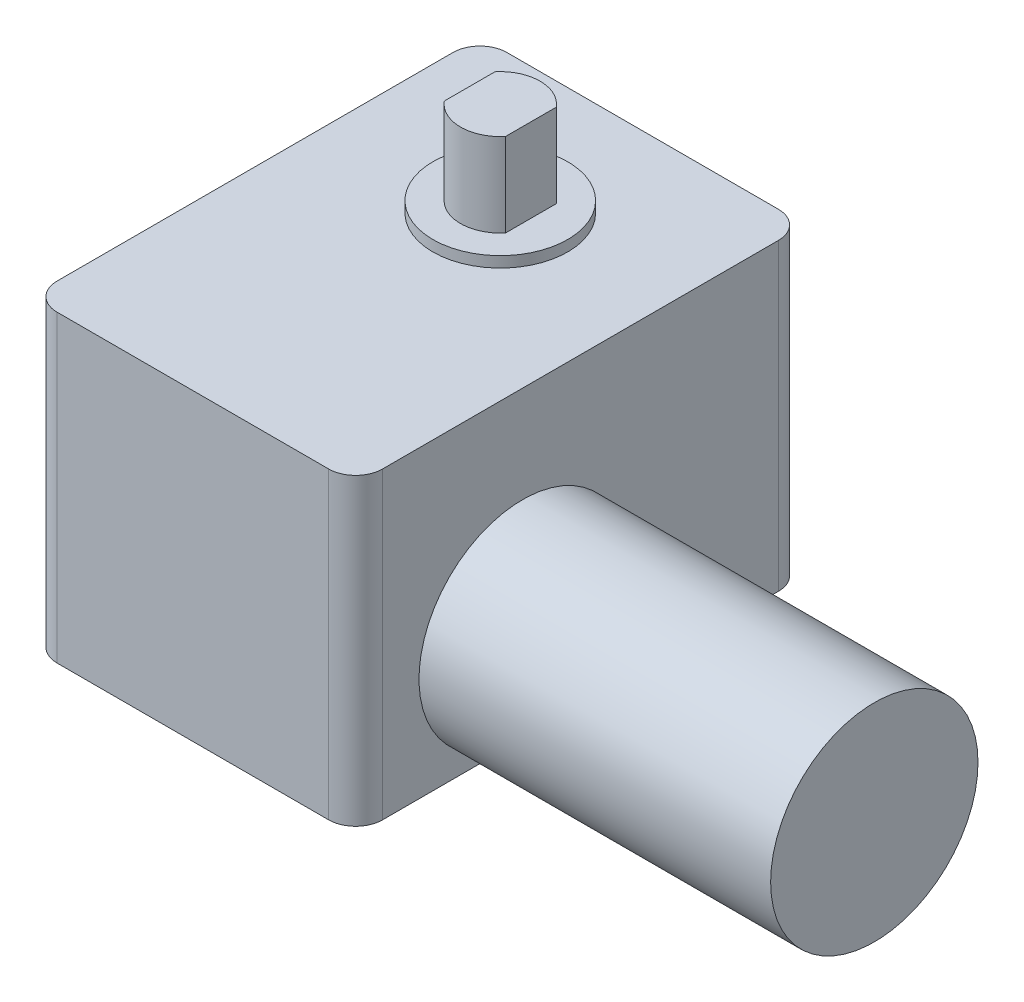
SolidWorks part; units mm, degrees
material "Delrin 2700 NC010, Low Viscosity Acetal Copolymer (SS)"
ref_plane "Front Plane" through (0, 0, 0) normal (0, 0, 1) x (1, 0, 0)
ref_plane "Top Plane" through (0, 0, 0) normal (0, 1, 0) x (1, 0, 0)
ref_plane "Right Plane" through (0, 0, 0) normal (1, 0, 0) x (0, 0, -1)
sketch "Sketch2" plane through (0, 0, 0) normal (0, 1, 0) x (1, 0, 0)
  line L0 (0, 0) -> (0, 16.68)
  line L1 (0, 0) -> (12.07, 0)
  line L2 (0, 16.68) -> (12.07, 16.68)
  line L3 (12.07, 0) -> (12.07, 16.68)
  line L4 (12.07, 2.35) -> (12.07, 10.04)
  line L5 (12.07, 2.35) -> (25.11, 2.35)
  line L7 (25.11, 2.35) -> (25.11, 6.195)
  line L8 (4.8983, 12.34) -> (4.8983, 10.46)
  line L9 (7.1717, 12.34) -> (7.1717, 10.46)
  line L10 (25.11, 6.195) -> (12.07, 6.195)
  circle A0 centre (6.035, 11.4) radius 2.5
  arc A1 (4.8983, 10.46) -> (7.1717, 10.46) centre (6.035, 11.4) ccw
  arc A2 (7.1717, 12.34) -> (4.8983, 12.34) centre (6.035, 11.4) ccw
  point P11 (6.035, 16.68)
  dimension "D7" = 5
  dimension "D8" = 2.95
  dimension "D1" = 12.07
  dimension "D2" = 16.68
  dimension "D3" = 2.35
  dimension "D4" = 3.845
  dimension "D5" = 25.11
  dimension "D6" = 11.4
  dimension "D9" = 1.88
revolve "Revolve1" add sketch "Sketch2" angle 360 about L10 region at (18.59, 0, -4.2725)
extrude "Boss-Extrude1" add sketch "Sketch2<5>" against normal blind 3.845 contours L1 L3 L4 L2 L0 A0 | A0 A2 L9 A1 L8 | L9 A2 L8 A1 region at (6.035, 0, -8.0093) region at (6.035, 0, -11.4) region at (3.6057, 0, -11.4)
sketch "Sketch2<5>" plane through (0, 0, 0) normal (0, 1, 0) x (1, 0, 0) same geometry as "Sketch2"
extrude "Boss-Extrude2" add sketch "Sketch2<6>" along normal blind 7.425 contours L1 L3 L4 L2 L0 A0 region at (6.035, 0, -8.0093)
sketch "Sketch2<6>" plane through (0, 0, 0) normal (0, 1, 0) x (1, 0, 0) same geometry as "Sketch2"
extrude "Boss-Extrude3" add sketch "Sketch2<7>" along normal blind 7.825 contours A0 A2 L9 A1 L8 region at (3.6057, 0, -11.4)
sketch "Sketch2<7>" plane through (0, 0, 0) normal (0, 1, 0) x (1, 0, 0) same geometry as "Sketch2"
extrude "Boss-Extrude4" add sketch "Sketch2<8>" along normal blind 10.925 contours L9 A2 L8 A1 region at (6.035, 0, -11.4)
sketch "Sketch2<8>" plane through (0, 0, 0) normal (0, 1, 0) x (1, 0, 0) same geometry as "Sketch2"
fillet "Fillet1" radius 1 4 edges at (0, 1.79, 0) (12.07, 1.79, 0) (12.07, 1.79, -16.68) (0, 1.79, -16.68)
equation "\"whitemotordepth\"=11.27mm"
equation "\"D1@Boss-Extrude2\"=\"whitemotordepth\" - \"whitemotorbackdepth\""
equation "\"whitemotorbackdepth\"=3.845mm"
equation "\"D1@Boss-Extrude1\"=\"whitemotorbackdepth\""
equation "\"D1@Boss-Extrude3\"=\"whitemotordepth\"-\"whitemotorbackdepth\"+.4"
equation "\"whitemotoraxledepth\" = 3.5mm"
equation "\"D1@Boss-Extrude4\"=\"whitemotoraxledepth\"+\"whitemotordepth\"-\"whitemotorbackdepth\""
equation "\"whitemotoraxleoffset\"=11.4mm"
equation "\"D6@Sketch2\"=\"whitemotoraxleoffset\""
equation "\"whitemotorwidth\"=12.07mm"
equation "\"D1@Sketch2\"=\"whitemotorwidth\""
equation "\"whitemotorheight\"=16.68mm"
equation "\"D2@Sketch2\"=\"whitemotorheight\""
equation "\"whitemotorcylinderlength\" =13.04mm"
equation "\"D5@Sketch2\"=\"whitemotorcylinderlength\"+\"whitemotorwidth\""
equation "\"whitemotorcylinderradius\"=3.845mm"
equation "\"D4@Sketch2\"=\"whitemotorcylinderradius\""
equation "\"whitemotorcylinderoffset\"=2.35mm"
equation "\"D3@Sketch2\"=\"whitemotorcylinderoffset\""
equation "\"whitemotorcutoutlength\"=1.88mm"
equation "\"D9@Sketch2\"=\"whitemotorcutoutlength\""
equation "\"whitemotorouterrad\"=5mm"
equation "\"D7@Sketch2\"=\"whitemotorouterrad\""
equation "\"whitemotorinnerrad\"=2.95mm"
equation "\"D8@Sketch2\"=\"whitemotorinnerrad\""
equation "\"CageLeftBottomEdge\"=22.11mm"
equation "\"CageLeftTopEdge\"=22.11mm"
equation "\"CageRightBottomEdge\"=21.63mm"
equation "\"CageRightTopEdge\"=21.63mm"
equation "\"CageHeight\"=86.04mm"
equation "\"CageLength\"=73.76mm"
equation "\"CageTopScrewClearance\"=10mm"
equation "\"CageBottomScrewClearance\"=25mm"
equation "\"CageLeftTopDepth\"= 11.65mm"
equation "\"CageLeftBottomDepth\"=11.11mm"
equation "\"CageLeftTopHeight\"=8.56175mm"
equation "\"CageLeftBottomHeight\"=16mm"
equation "\"CageRightTopDepth\"= 11.05mm"
equation "\"CageRightBottomDepth\"=10.58mm"
equation "\"CageRightTopHeight\"=9.6mm"
equation "\"CageRightBottomHeight\"=15.49mm"
equation "\"CageLeftTopChannelDepth\"=2.41908mm"
equation "\"CageLeftBottomChannelDepth\"=2.588mm"
equation "\"CageLeftChannelHeight\"=11.7mm"
equation "\"CageRightTopChannelDepth\"=2.32mm"
equation "\"CageRightBottomChannelDepth\"=2.318mm"
equation "\"CageRightChannelHeight\"=10mm"
equation "\"CageChanRelHeight\"=23.99mm"
equation "\"CageChanRelDepth\"=5.492mm"
equation "\"CageChamberRadius\"=16.261mm"
equation "\"CageScrewDiameter\"=4.8mm"
equation "\"CageSetScrewDiameter\"=3.5mm"
equation "\"CageAxleRadius\"=6.639mm"
equation "\"CageAxleKeyHeight\"=1.619mm"
equation "\"CageAxleKeyWidth\"=2.662mm"
equation "\"CageHoseWindowWidth\"=16.29mm"
equation "\"CageHoseWindowHeight\"=26.5mm"
equation "\"CageHoseWindow-Edge\"=8.89mm"
equation "\"CageScrew-VerticalEdge\"=5.0mm"
equation "\"CageScrew-HorizontalEdge\"=7.5mm"
equation "\"CageScrew-HoseCornerScrewEdge\"=4.45mm"
equation "\"CageAxle-BottomEdge\"=56.05mm"
equation "\"CageAxle-FrontEdge\"=46.03mm"
equation "\"CageBackSetScrew-Axle\"=40mm"
equation "\"CageFrontSetScrew-Axle\"=22mm"
equation "\"CageVelocityWindow-BackEdge\"=34.8mm"
equation "\"CageVelocityWindow-BottomEdge\"=27.55mm"
equation "\"CageVelocityWindowHeight\"=22.29mm"
equation "\"CageVelocityWindowWidth\"=12.61mm"
equation "\"TriggerSlot-BottomEdge\"=6.35mm"
equation "\"TriggerSlot-FrontEdge\"=15mm"
equation "\"TriggerSlotSize\"=6.7mm"
equation "\"TriggerRackOffset\"=.236224in"
equation "\"TriggerSlotSizeInt\"=.25in"
equation "\"MotorMountLegLength\"=.25in"
equation "\"GearOffset\"=.264907in"
equation "\"TriggerSlotSpacing\"=.25in"
equation "\"TGMGearFaceDiameter\"=24.40mm"
equation "\"TGMCylinderLength\"=15.00mm"
equation "\"TGMScrewHole-Center\"=8.70mm"
equation "\"TGMScrewHoleDiameter\"=5.04mm"
equation "\"TGMCenterHoleDiameter\"=9.50mm"
equation "\"TGMShaftCollarSideLength\"=19.00mm"
equation "\"TGMShaftCollarDockingDepth\"=7.00mm"
equation "\"TriggerMiniSlotWidth\"=3.5mm"
equation "\"TriggerRackWidth\"=6.5mm"
equation "\"elasticracklength\"=2in"
equation "\"elasticrackpegsize\"=.25in"
equation "\"elasticrackpegbuffer\"=.125in"
equation "\"elasticrackpegspacing\"=1.76476378in"
equation "\"elasticbaybuffer\"=.25in"
equation "\"elasticdepth\"=.125in"
equation "\"elasticbaydepth\"=.75in"
equation "\"motormountwidth\"=12mm"
equation "\"motormountcornerfillet\"=3mm"
equation "\"pandiscradius\"=14in"
equation "\"towermaterialwidth\"=.25in"
equation "\"towerslotlength\"=.5in"
equation "\"towermarkerspace\"=5in"
equation "\"towerslothorizoffset\"=1in"
equation "\"towerslothorizspacing\"=2in"
equation "\"towerslotvertoffset\"=3in"
equation "\"towerslotvertspacing\"=2in"
equation "\"towerheight\"=12in"
equation "\"towerupslot\"=1in"
equation "\"toweraxle\"=.5in"
equation "\"towerplatslotoffset\"=1.5in"
equation "\"towermotorpanelheight\"=10in"
equation "\"towerplatdepth\"=2in"
equation "\"stepperouterrad\"=10mm"
equation "\"stepperscrewsize\"=3.45mm"
equation "\"stepperscrewc2c\"=49.5mm"
equation "\"stepperdepthoffset\"=24mm"
equation "\"stepperhorizoffset\"=22.91mm"
equation "\"shaftslotOD\"=18.8mm"
equation "\"shaftslotID\"=13.28mm"
equation "\"shaftkeywidth\"=2.67mm"
equation "\"shaftkeydepth\"=1.8mm"
equation "\"shaftcollartotaldepth\"=12.5mm"
equation "\"shaftsquaredepth\"=6mm"
equation "\"shaftsetscrewsize\"=3.5mm"
equation "\"shaftkeytightdepth\"=1.85mm"
equation "\"shaftslottightID\"=12.78mm"
equation "\"shaftsetscrewoffset\"=9mm"
equation "\"cagecollartotaldepth\"=10mm"
equation "\"cagecollartotalwidth\"=35mm"
equation "\"cagecollarbasedepth\"=4mm"
